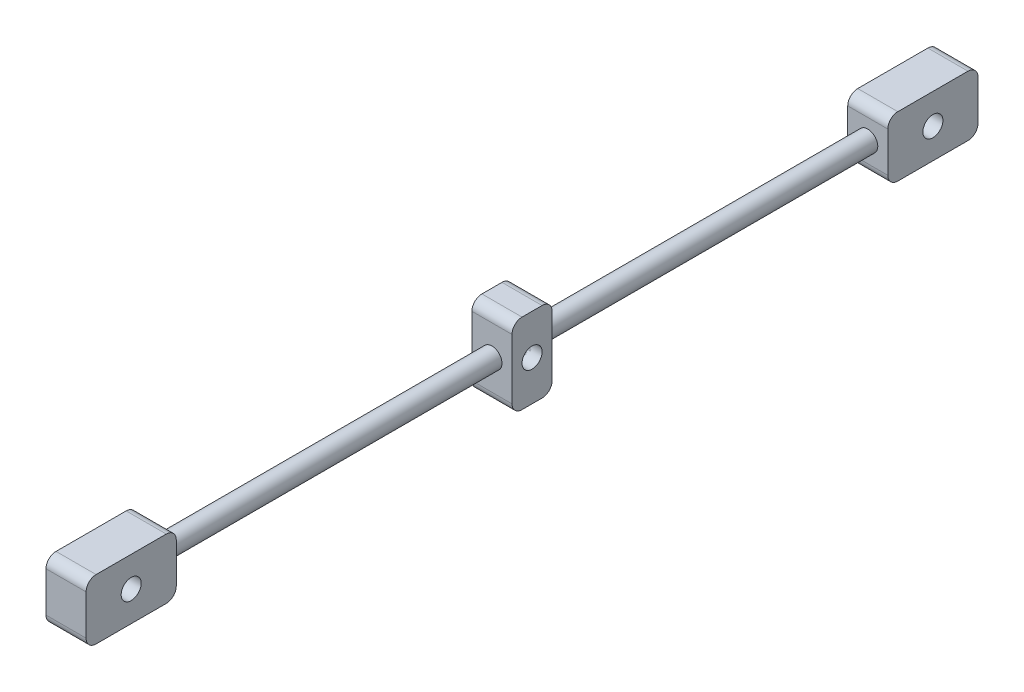
SolidWorks part; units mm, degrees
ref_plane "Front Plane" through (0, 0, 0) normal (1, 0, 0) x (0, 1, 0)
ref_plane "Top Plane" through (0, 0, 0) normal (0, 0, 1) x (0, 1, 0)
ref_plane "Right Plane" through (0, 0, 0) normal (0, 1, 0) x (-1, 0, 0)
sketch "Sketch1" plane through (0, 0, 0) normal (0, 0, 1) x (0, 1, 0)
  circle A0 centre (0, 0) radius 10
  dimension "D1" = 20
extrude "Boss-Extrude1" add sketch "Sketch1" along normal blind 400
sketch "Sketch2" plane through (0, 0, 0) normal (1, 0, 0) x (0, 1, 0)
  line L1 (40, 20) -> (-40, 20)
  line L2 (40, 20) -> (40, -20)
  line L3 (40, -20) -> (-40, -20)
  line L4 (-40, 20) -> (-40, -20)
  line L5 (40, 20) -> (-40, -20) construction
  line L6 (40, -20) -> (-40, 20) construction
  point P0 (0, 0)
  dimension "D1" = 40
  dimension "D2" = 80
extrude "Boss-Extrude2" add sketch "Sketch2" along normal blind 20 and the other way blind 20 separate body
mirror "Mirror1" about plane through (0, 0, 0) normal (0, 0, 1) of "Boss-Extrude1"
sketch "Sketch3" plane through (0, 0, 0) normal (1, 0, 0) x (0, 1, 0)
  line L0 (-10, -400) -> (10, -400) construction
  line L1 (30, -445) -> (-30, -445)
  line L2 (30, -445) -> (30, -355)
  line L3 (30, -355) -> (-30, -355)
  line L4 (-30, -445) -> (-30, -355)
  line L5 (30, -445) -> (-30, -355) construction
  line L6 (30, -355) -> (-30, -445) construction
  point P0 (0, -400)
  dimension "D1" = 60
  dimension "D2" = 90
extrude "Boss-Extrude3" add sketch "Sketch3" along normal blind 20 and the other way blind 20
mirror "Mirror2" about plane through (0, 0, 0) normal (0, 0, 1) of "Boss-Extrude3"
sketch "Sketch4" plane through (-20, 0, 0) normal (-1, 0, 0) x (0, -1, 0)
  line L0 (30, -445) -> (-30, -445) construction
  line L1 (30, -355) -> (30, -445) construction
  line L4 (0, 0) -> (-40, 0) construction
  line L5 (-40, -20) -> (-40, 20) construction
  circle A0 centre (0, -400) radius 10
  circle A1 centre (0, 400) radius 10
  dimension "D2" = 20
  dimension "D1" = 45
  dimension "D3" = 30
extrude "Cut-Extrude1" cut sketch "Sketch4" against normal blind 54
sketch "Sketch5" plane through (-20, 0, 0) normal (-1, 0, 0) x (0, -1, 0)
  circle A0 centre (0, 0) radius 10
  dimension "D1" = 20
extrude "Cut-Extrude4" cut sketch "Sketch5" against normal blind 54
fillet "Fillet1" radius 10 4 edges at (0, -30, -445) (0, 30, -445) (0, 30, -355) (0, -30, -355)
fillet "Fillet2" radius 10 4 edges at (0, -40, -20) (0, 40, -20) (0, 40, 20) (0, -40, 20)
fillet "Fillet3" radius 10 4 edges at (0, -30, 355) (0, 30, 355) (0, -30, 445) (0, 30, 445)
